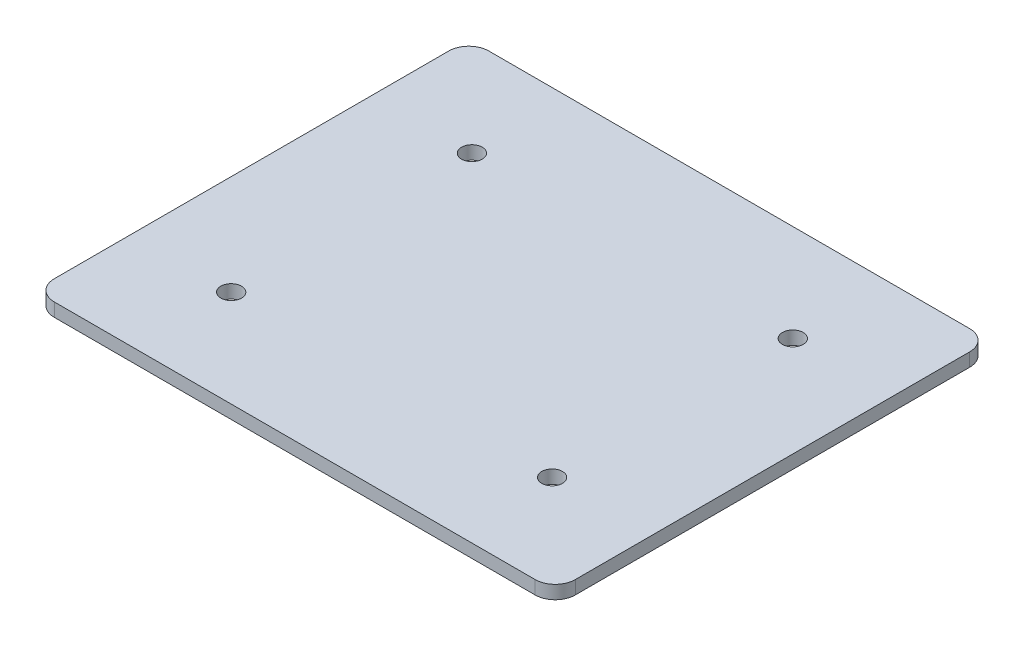
SolidWorks part; units mm, degrees
ref_plane "Front Plane" through (0, 0, 0) normal (0, 0, 1) x (1, 0, 0)
ref_plane "Top Plane" through (0, 0, 0) normal (0, 1, 0) x (1, 0, 0)
ref_plane "Right Plane" through (0, 0, 0) normal (1, 0, 0) x (0, 0, -1)
sketch "Sketch1" plane through (0, 0, 0) normal (0, 1, 0) x (1, 0, 0)
  line L1 (-38.9641, -32.5) -> (38.9641, -32.5)
  line L2 (-38.9641, -32.5) -> (-38.9641, 32.5)
  line L3 (-38.9641, 32.5) -> (38.9641, 32.5)
  line L4 (38.9641, -32.5) -> (38.9641, 32.5)
  line L5 (-38.9641, -32.5) -> (38.9641, 32.5) construction
  line L6 (-38.9641, 32.5) -> (38.9641, -32.5) construction
  line L7 (-24, 18) -> (24, 18)
  line L8 (-24, 18) -> (-24, -18)
  line L9 (-24, -18) -> (24, -18)
  line L10 (24, 18) -> (24, -18)
  line L11 (-24, 18) -> (24, -18) construction
  line L12 (-24, -18) -> (24, 18) construction
  circle A0 centre (-24, 18) radius 1.55
  circle A1 centre (24, 18) radius 1.55
  circle A2 centre (-24, -18) radius 1.55
  circle A3 centre (24, -18) radius 1.55
  point P0 (0, 0)
  point P6 (0, 0)
extrude "Boss-Extrude1" add sketch "Sketch1" along normal blind 2 contours L3 L4 L1 L2
sketch "Sketch2" plane through (0, 2, 0) normal (0, 1, 0) x (1, 0, 0)
  circle A0 centre (-24, 18) radius 1.55
  circle A1 centre (24, 18) radius 1.55
  circle A2 centre (24, -18) radius 1.55
  circle A3 centre (-24, -18) radius 1.55
extrude "Cut-Extrude3" cut sketch "Sketch2" against normal through all both and the other way through all
fillet "Fillet1" radius 3 4 edges at (-38.9641, 1, 32.5) (38.9641, 1, 32.5) (38.9641, 1, -32.5) (-38.9641, 1, -32.5)
